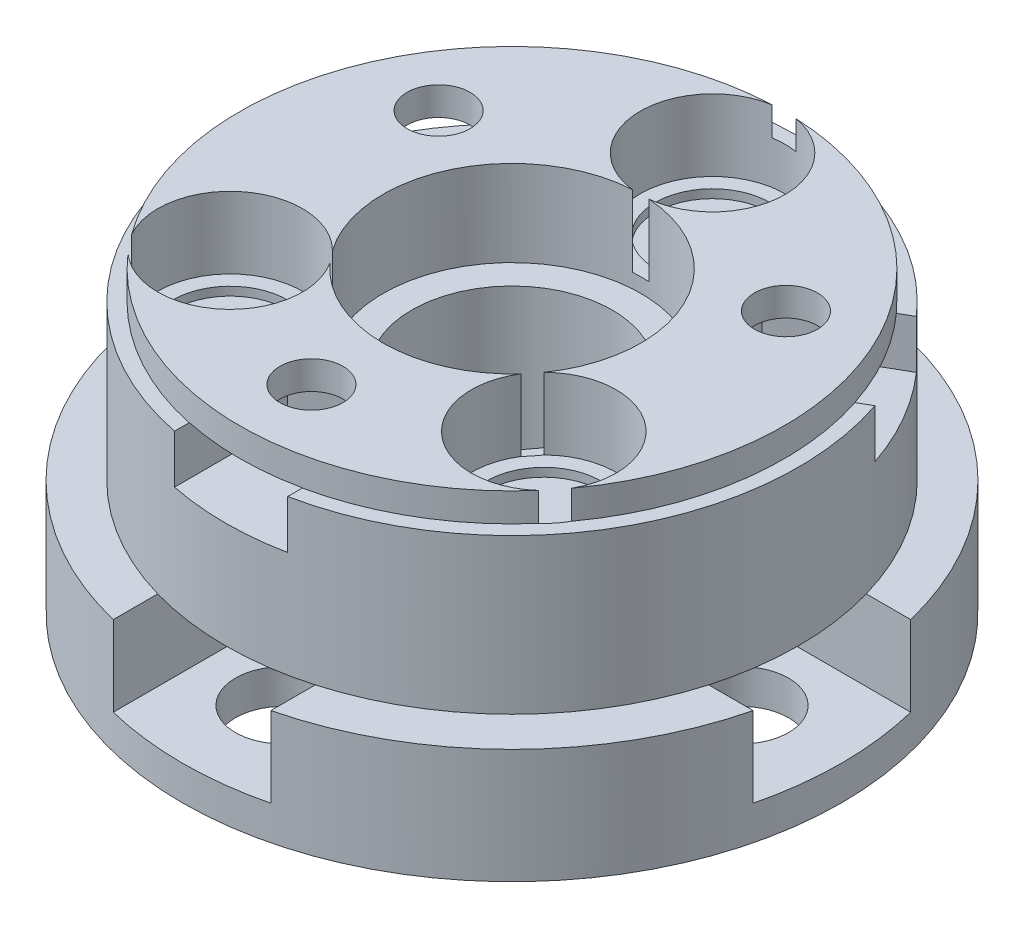
SolidWorks part; units mm, degrees
ref_plane "Front Plane" through (0, 0, 0) normal (0, 0, 1) x (1, 0, 0)
ref_plane "Top Plane" through (0, 0, 0) normal (0, 1, 0) x (1, 0, 0)
ref_plane "Right Plane" through (0, 0, 0) normal (1, 0, 0) x (0, 0, -1)
sketch "Sketch2" plane through (0, 0, 0) normal (0, 1, 0) x (1, 0, 0)
  circle A0 centre (0, 0) radius 11.5
  dimension "D1" = 23
extrude "Boss-Extrude1" add sketch "Sketch2" along normal blind 1
sketch "Sketch3" plane through (0, 1, 0) normal (0, 1, 0) x (1, 0, 0)
  circle A0 centre (0, 0) radius 10
  dimension "D1" = 20
extrude "Boss-Extrude2" add sketch "Sketch3" along normal blind 4
ref_plane "Plane1" through (0, 4.9, 0) normal (0, -1, 0) x (-1, 0, 0)
sketch "Sketch4" plane through (0, 4.9, 0) normal (0, -1, 0) x (-1, 0, 0)
  circle A0 centre (0, 0) radius 7 construction
  circle A1 centre (0, 7) radius 2.525
  dimension "D1" = 14
  dimension "D2" = 5.05
extrude "Cut-Extrude1" cut sketch "Sketch4" against normal through all
sketch "Sketch5" plane through (0, 4.9, 0) normal (0, 1, 0) x (1, 0, 0)
  circle A0 centre (0, 7) radius 2
  dimension "D1" = 4
extrude "Cut-Extrude2" cut sketch "Sketch5" against normal blind 0.3
ref_axis "Axis1" through (0, 5, 0) along (0, -1, 0)
pattern_circular "CirPattern1" count 14 over 360 about axis through (0, 5, 0) along (0, -1, 0) skipping 1, 2, 3, 4, 6, 7, 8, 10, 11, 12, 13 of "Cut-Extrude1", "Cut-Extrude2"
sketch "Sketch7" plane through (0, 4.9, 0) normal (0, 1, 0) x (1, 0, 0)
  circle A0 centre (5.4728, -4.3644) radius 2.525 construction
  circle A1 centre (0, 0) radius 10
  circle A3 centre (-5.4728, -4.3644) radius 2.525 construction
  circle A4 centre (0, 7) radius 2.525 construction
  circle A5 centre (5.4728, -4.3644) radius 2.525
  circle A6 centre (-5.4728, -4.3644) radius 2.525
  circle A7 centre (0, 7) radius 2.525
  circle A9 centre (0, 0) radius 10
  dimension "D1" = 0
extrude "Boss-Extrude4" add sketch "Sketch7" along normal blind 1.5
sketch "Sketch6" plane through (0, 6.4, 0) normal (0, 1, 0) x (1, 0, 0)
  circle A0 centre (0, 0) radius 4.5 construction
  arc A1 (-0.4128, 9.491) -> (-0.284, 4.491) centre (0, 7) ccw
  circle A2 centre (0, 0) radius 9.5 construction
  arc A3 (-3.6883, -2.578) -> (-7.6778, -5.5948) centre (-5.4728, -4.3644) ccw
  arc A4 (3.3341, -3.0222) -> (7.163, -6.2403) centre (5.4728, -4.3644) ccw
  arc A5 (0.284, 4.491) -> (0.4128, 9.491) centre (0, 7) ccw
  arc A6 (-7.163, -6.2403) -> (-3.3341, -3.0222) centre (-5.4728, -4.3644) ccw
  arc A7 (7.6778, -5.5948) -> (3.6883, -2.578) centre (5.4728, -4.3644) ccw
  arc A8 (-3.6883, -2.578) -> (-0.284, 4.491) centre (0, 0) cw
  arc A9 (-7.6778, -5.5948) -> (-0.4128, 9.491) centre (0, 0) cw
  arc A12 (-3.3341, -3.0222) -> (3.3341, -3.0222) centre (0, 0) ccw
  arc A13 (-7.163, -6.2403) -> (7.163, -6.2403) centre (0, 0) ccw
  arc A14 (0.284, 4.491) -> (3.6883, -2.578) centre (0, 0) cw
  arc A15 (0.4128, 9.491) -> (7.6778, -5.5948) centre (0, 0) cw
  dimension "D1" = 9
  dimension "D2" = 5.05
  dimension "D3" = 19
extrude "Boss-Extrude3" add sketch "Sketch6" along normal up to surface (0.998 mm away)
sketch "Sketch8" plane through (0, 7.398, 0) normal (0, 1, 0) x (1, 0, 0)
  circle A0 centre (0, -7) radius 1.1 construction
  circle A1 centre (0, -7) radius 1.1
extrude "Cut-Extrude3" cut sketch "Sketch8" against normal offset from surface (2.69 mm away) 12.2
sketch "Sketch9" plane through (0, 4.708, 0) normal (0, 1, 0) x (1, 0, 0)
  line L0 (-1.975, -8.1403) -> (-1.975, -11.3291)
  line L1 (0, -9.2805) -> (1.975, -8.1403) construction
  line L2 (1.975, -8.1403) -> (1.975, -5.8597)
  line L3 (1.975, -5.8597) -> (0, -4.7195)
  line L4 (0, -4.7195) -> (-1.975, -5.8597)
  line L5 (-1.975, -5.8597) -> (-1.975, -8.1403)
  line L6 (-1.975, -8.1403) -> (0, -9.2805) construction
  line L7 (-1.975, -11.3291) -> (1.975, -11.3291)
  line L8 (1.975, -11.3291) -> (1.975, -8.1403)
  circle A0 centre (0, -7) radius 1.975 construction
  circle A1 centre (0, 0) radius 11.5 construction
  dimension "D1" = 3.95
extrude "Cut-Extrude4" cut sketch "Sketch9" along normal blind 1.7 contours L7 L8 L2 L3 L4 L5 L0
pattern_circular "CirPattern2" count 3 over 360 about axis through (0, 5, 0) along (0, -1, 0) of "Cut-Extrude4", "Cut-Extrude3"
sketch "Sketch10" plane through (0, 0, 0) normal (0, -1, 0) x (1, 0, 0)
  circle A0 centre (0, 0) radius 8 construction
  circle A1 centre (0, 8) radius 1.35
  dimension "D1" = 16
  dimension "D2" = 2.7
sketch "Sketch11" plane through (0, 0, 0) normal (0, -1, 0) x (1, 0, 0)
  circle A1 centre (0, 0) radius 11.5
  circle A2 centre (0, 0) radius 11.5
  dimension "D1" = 0
extrude "Boss-Extrude5" add sketch "Sketch11" along normal blind 3
sketch "Sketch12" plane through (0, -3, 0) normal (0, -1, 0) x (1, 0, 0)
  circle A0 centre (0, 8) radius 1.65
  dimension "D1" = 3.3
extrude "Cut-Extrude5" cut sketch "Sketch12" against normal up to surface (4 mm away) up to face at (0, 1, 10)
sketch "Sketch13" plane through (0, 1, 0) normal (0, 1, 0) x (1, 0, 0)
  line L0 (-2.75, -9.5877) -> (-2.75, -11.5)
  line L1 (0, -11.1754) -> (2.75, -9.5877) construction
  line L2 (2.75, -9.5877) -> (2.75, -6.4123)
  line L3 (2.75, -6.4123) -> (0, -4.8246)
  line L4 (0, -4.8246) -> (-2.75, -6.4123)
  line L5 (-2.75, -6.4123) -> (-2.75, -9.5877)
  line L6 (-2.75, -9.5877) -> (0, -11.1754) construction
  line L7 (-2.75, -11.5) -> (2.75, -11.5)
  line L8 (2.75, -11.5) -> (2.75, -9.5877)
  circle A0 centre (0, -8) radius 2.75 construction
  circle A1 centre (0, 0) radius 11.5 construction
  dimension "D1" = 5.5
extrude "Cut-Extrude6" cut sketch "Sketch13" against normal blind 2.8
pattern_circular "CirPattern3" count 4 over 360 about axis through (0, 5, 0) along (0, -1, 0) of "Cut-Extrude5", "Cut-Extrude6"
sketch "Sketch14" [suppressed] plane through (0, 0, 0) normal (0, -1, 0) x (1, 0, 0)
  circle A0 centre (0, 0) radius 7 construction
  circle A1 centre (0, 7) radius 1.4
  dimension "14" = 14
  dimension "D2" = 2.8
extrude "Cut-Extrude7" [suppressed] cut sketch "Sketch14" against normal blind 4
sketch "Sketch15" [suppressed] plane through (0, 4, 0) normal (0, -1, 0) x (1, 0, 0)
  line L1 (0, 4.0555) -> (2.55, 5.5278)
  line L2 (2.55, 5.5278) -> (2.55, 8.4722)
  line L3 (2.55, 8.4722) -> (0, 9.9445) construction
  line L4 (0, 9.9445) -> (-2.55, 8.4722) construction
  line L5 (-2.55, 8.4722) -> (-2.55, 5.5278)
  line L6 (-2.55, 5.5278) -> (0, 4.0555)
  line L9 (2.55, 11.5) -> (-2.55, 11.5)
  line L10 (-2.55, 8.4722) -> (-2.55, 11.5)
  line L11 (2.55, 8.4722) -> (2.55, 11.5)
  circle A0 centre (0, 7) radius 2.55 construction
  circle A2 centre (0, 0) radius 11.5 construction
  dimension "D1" = 5.1
extrude "Cut-Extrude8" [suppressed] cut sketch "Sketch15" along normal blind 2.4
pattern_circular "CirPattern4" [suppressed] count 3 over 360 about axis through (0, 5, 0) along (0, -1, 0) of bodies 117
sketch "Sketch16" plane through (0, 6.4, 0) normal (0, 1, 0) x (1, 0, 0)
  circle A0 centre (0, 0) radius 4.5
  arc A1 (3.6883, -2.578) -> (0.284, 4.491) centre (0, 0) ccw construction
extrude "Cut-Extrude9" cut sketch "Sketch16" against normal blind 2
sketch "Sketch17" plane through (0, 4.4, 0) normal (0, 1, 0) x (1, 0, 0)
  circle A0 centre (0, 0) radius 3.5
  dimension "D1" = 7
extrude "Cut-Extrude10" cut sketch "Sketch17" against normal through all
